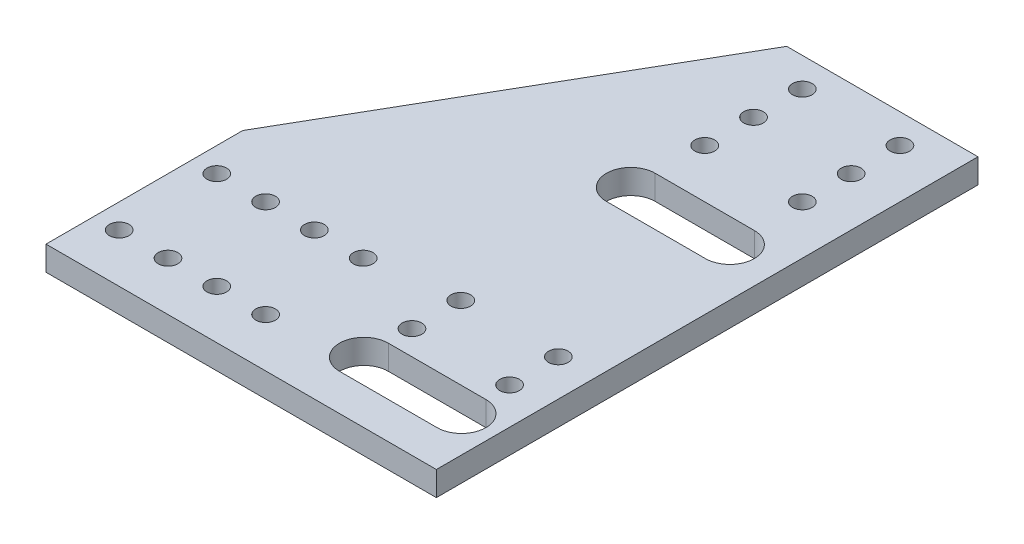
SolidWorks part; units mm, degrees
material "6061-T6 (SS)"
ref_plane "Front Plane" through (0, 0, 0) normal (0, 0, 1) x (1, 0, 0)
ref_plane "Top Plane" through (0, 0, 0) normal (0, 1, 0) x (1, 0, 0)
ref_plane "Right Plane" through (0, 0, 0) normal (1, 0, 0) x (0, 0, -1)
sketch "Sketch1" plane through (0, 0, 0) normal (0, 1, 0) x (1, 0, 0)
  line L1 (0, 0) -> (101.6, 0)
  line L2 (0, 0) -> (0, 152.4)
  line L3 (0, 152.4) -> (101.6, 152.4)
  line L4 (101.6, 0) -> (101.6, 152.4)
  dimension "D1" = 101.6
  dimension "D2" = 152.4
extrude "Boss-Extrude1" add sketch "Sketch1" along normal blind 6.35
sketch "Sketch2" plane through (0, 0, 0) normal (0, -1, 0) x (-1, 0, 0)
  line L0 (-101.6, 0) -> (-101.6, 152.4) construction
  line L1 (-101.6, 152.4) -> (0, 152.4) construction
  circle A0 centre (-88.9, 146.05) radius 2.5527
  circle A1 centre (-88.9, 133.35) radius 2.5527
  circle A2 centre (-88.9, 120.65) radius 2.5527
  circle A3 centre (-88.9, 107.95) radius 2.5527
  circle A4 centre (-63.5, 133.35) radius 2.5527
  circle A5 centre (-63.5, 120.65) radius 2.5527
  circle A6 centre (-63.5, 107.95) radius 2.5527
  circle A7 centre (-63.5, 146.05) radius 2.5527
  dimension "D1" = 12.7
  dimension "D2" = 6.35
  dimension "D3" = 5.1054
  dimension "D6" = 12.7
  dimension "D8" = 31.75
  dimension "D4" = 4
  dimension "D5" = 2
extrude "Cut-Extrude1" cut sketch "Sketch2" against normal through all
sketch "Sketch3" plane through (0, 0, 0) normal (0, -1, 0) x (-1, 0, 0)
  line L0 (-89.0905, 88.9) -> (-63.3095, 88.9) construction
  line L1 (-89.0905, 95.25) -> (-63.3095, 95.25)
  line L2 (-89.0905, 82.55) -> (-63.3095, 82.55)
  line L4 (-101.6, 0) -> (-101.6, 152.4) construction
  line L5 (0, 0) -> (-101.6, 0) construction
  arc A0 (-89.0905, 95.25) -> (-89.0905, 82.55) centre (-89.0905, 88.9) ccw
  arc A1 (-63.3095, 82.55) -> (-63.3095, 95.25) centre (-63.3095, 88.9) ccw
  point P4 (-76.2, 88.9)
  point P9 (0, 0)
  point P10 (0, 0)
  point P11 (0, 0)
  dimension "D2" = 12.5095
  dimension "D1" = 12.7
  dimension "D3" = 82.55
extrude "Cut-Extrude2" cut sketch "Sketch3" against normal through all
sketch "Sketch4" plane through (0, 0, 0) normal (0, -1, 0) x (-1, 0, 0)
  line L0 (-101.6, 0) -> (-101.6, 152.4) construction
  line L1 (0, 0) -> (-101.6, 0) construction
  circle A0 centre (-92.075, 41.275) radius 2.5527
  circle A1 centre (-66.675, 41.275) radius 2.5527
  circle A2 centre (-66.675, 28.575) radius 2.5527
  circle A3 centre (-92.075, 28.575) radius 2.5527
  dimension "D1" = 5.1054
  dimension "D2" = 9.525
  dimension "D3" = 41.275
  dimension "D6" = 12.7
  dimension "D7" = 34.925
  dimension "D8" = 25.4
  dimension "D4" = 2
  dimension "D5" = 2
extrude "Cut-Extrude3" cut sketch "Sketch4" against normal through all
sketch "Sketch5" plane through (0, 0, 0) normal (0, -1, 0) x (-1, 0, 0)
  line L0 (-92.2655, 15.875) -> (-66.8655, 15.875) construction
  line L1 (-92.2655, 22.225) -> (-66.8655, 22.225)
  line L2 (-92.2655, 9.525) -> (-66.8655, 9.525)
  line L3 (0, 0) -> (-101.6, 0) construction
  line L4 (-101.6, 0) -> (-101.6, 152.4) construction
  arc A0 (-92.2655, 22.225) -> (-92.2655, 9.525) centre (-92.2655, 15.875) ccw
  arc A1 (-66.8655, 9.525) -> (-66.8655, 22.225) centre (-66.8655, 15.875) ccw
  point P4 (-79.5655, 15.875)
  point P9 (0, 0)
  point P10 (0, 0)
  dimension "D1" = 12.7
  dimension "D2" = 9.525
  dimension "D3" = 9.3345
  dimension "D4" = 34.7345
extrude "Cut-Extrude4" cut sketch "Sketch5" against normal through all
sketch "Sketch6" plane through (0, 0, 0) normal (0, -1, 0) x (-1, 0, 0)
  line L0 (0, 0) -> (-101.6, 0) construction
  line L1 (-101.6, 0) -> (-101.6, 152.4) construction
  line L4 (0, 152.4) -> (0, 0) construction
  circle A0 centre (-44.45, 38.1) radius 2.5527
  circle A1 centre (-31.75, 38.1) radius 2.5527
  circle A2 centre (-19.05, 38.1) radius 2.5527
  circle A3 centre (-31.75, 12.7) radius 2.5527
  circle A4 centre (-19.05, 12.7) radius 2.5527
  circle A5 centre (-44.45, 12.7) radius 2.5527
  circle A6 centre (-6.35, 38.1) radius 2.5527
  circle A7 centre (-6.35, 12.7) radius 2.5527
  dimension "D1" = 5.1054
  dimension "D2" = 38.1
  dimension "D3" = 57.15
  dimension "D6" = 12.7
  dimension "D7" = 25.4
  dimension "D8" = 44.45
  dimension "D4" = 4
  dimension "D5" = 2
extrude "Cut-Extrude5" cut sketch "Sketch6" against normal through all
sketch "Sketch7" plane through (0, 0, 0) normal (0, -1, 0) x (-1, 0, 0)
  line L0 (-58.42, 152.4) -> (0, 152.4)
  line L2 (-101.6, 152.4) -> (0, 152.4) construction
  line L6 (0, 152.4) -> (0, 51.2136)
  line L7 (0, 51.2136) -> (-58.42, 152.4)
  dimension "D1" = 60
  dimension "D2" = 116.84
extrude "Cut-Extrude6" cut sketch "Sketch7" against normal through all and the other way through all
sketch "Sketch8" plane through (0, 0, 0) normal (0, -1, 0) x (-1, 0, 0)
  line L0 (-101.6, 152.4) -> (-58.42, 152.4)
  line L1 (-58.42, 152.4) -> (-51.8209, 140.97)
  line L2 (-58.42, 152.4) -> (0, 51.2136) construction
  line L3 (-51.8209, 140.97) -> (-101.6, 140.97)
  line L4 (-101.6, 0) -> (-101.6, 152.4) construction
  line L5 (-101.6, 140.97) -> (-101.6, 152.4)
  dimension "D1" = 11.43
extrude "Cut-Extrude7" cut sketch "Sketch8" against normal through all
